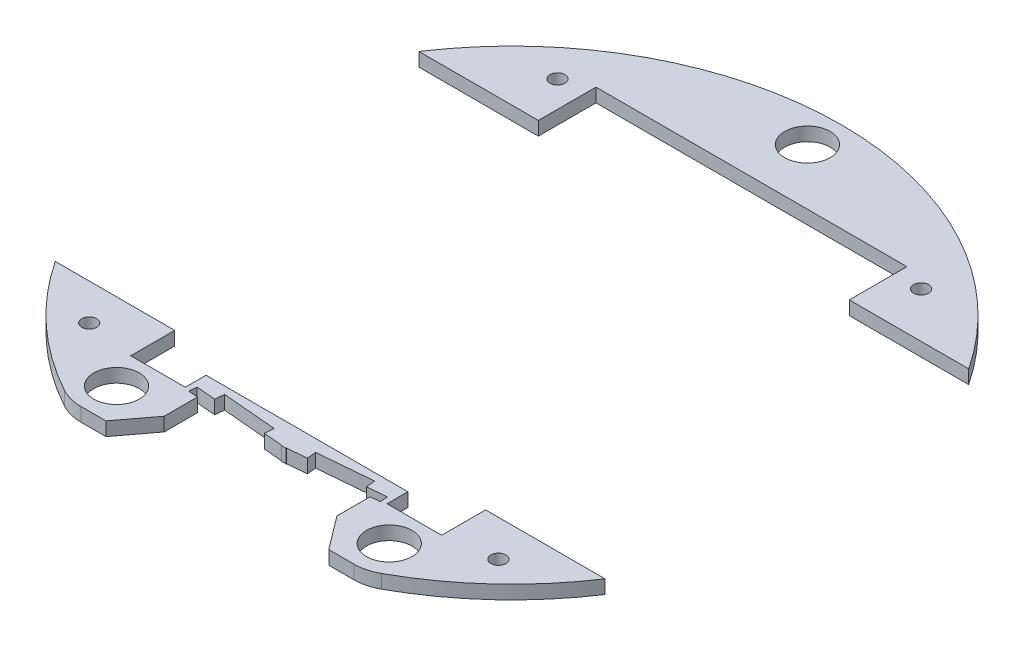
SolidWorks part; units mm, degrees
ref_plane "Front Plane" through (0, 0, 0) normal (0, 0, 1) x (1, 0, 0)
ref_plane "Top Plane" through (0, 0, 0) normal (0, 1, 0) x (1, 0, 0)
ref_plane "Right Plane" through (0, 0, 0) normal (1, 0, 0) x (0, 0, -1)
sketch "Sketch1" plane through (0, 0, 0) normal (0, 1, 0) x (1, 0, 0)
  line L0 (-30.03, -64.8129) -> (30.03, -64.8129)
  line L1 (0, -85) -> (0, 0) construction
  line L2 (0, -85) -> (32.4891, -64.8129) construction
  arc A0 (34.8348, -63.5829) -> (-34.8348, -63.5829) centre (0, 0) ccw
  circle A1 centre (0, -85) radius 38.25 construction
  arc A2 (30.03, -64.8129) -> (34.8348, -63.5829) centre (30.03, -54.8129) ccw
  arc A3 (-30.03, -64.8129) -> (-34.8348, -63.5829) centre (-30.03, -54.8129) cw
  dimension "D1" = 145
  dimension "D2" = 76.5
  dimension "D4" = 10
  dimension "D3" = 85
extrude "Boss-Extrude1" add sketch "Sketch1" along normal blind 3
sketch "Sketch2" plane through (0, 3, 0) normal (0, 1, 0) x (1, 0, 0)
  line L5 (22.2, -49.6757) -> (22.2, -45.1)
  line L6 (22.2, -45.1) -> (-22.2, -45.1)
  line L7 (-22.2, -45.1) -> (-22.2, -49.6757)
  line L8 (22.2, 49.6757) -> (22.2, 45.5)
  line L9 (-34.2, -49.6757) -> (-22.2, -49.6757) construction
  line L10 (-34.2, -49.6757) -> (-34.2, 49.6757) construction
  line L11 (-34.2, 49.6757) -> (-22.2, 49.6757) construction
  line L19 (34.2, 49.6757) -> (22.2, 49.6757) construction
  line L20 (34.2, -49.6757) -> (34.2, 49.6757) construction
  line L21 (34.2, -49.6757) -> (22.2, -49.6757) construction
  line L22 (22.2, 45.5) -> (-22.2, 45.5)
  line L23 (-22.2, 45.5) -> (-22.2, 49.6757)
  line L35 (-34.2, -49.6757) -> (-22.2, -49.6757)
  line L36 (-34.2, -49.6757) -> (-34.2, 49.6757)
  line L37 (-34.2, 49.6757) -> (-22.2, 49.6757)
  line L55 (34.2, 49.6757) -> (22.2, 49.6757)
  line L56 (34.2, -49.6757) -> (34.2, 49.6757)
  line L57 (34.2, -49.6757) -> (22.2, -49.6757)
  dimension "D1" = 45.1
  dimension "D2" = 45.5
extrude "Cut-Extrude1" cut sketch "Sketch2" against normal through all contours L55 L37 L36 L35 L7 L6 L5 L57 L56 region at (0, 3, -0.1256)
sketch "Sketch3" plane through (0, 3, 0) normal (0, 1, 0) x (1, 0, 0)
  line L0 (-34.2, 40) -> (-34.2, -40)
  line L1 (-72.5, -40) -> (-34.2, -40)
  line L2 (-72.5, -40) -> (-72.5, 40)
  line L3 (-72.5, 40) -> (-34.2, 40)
  line L4 (72.5, -40) -> (72.5, 40)
  line L5 (-72.5, -40) -> (72.5, 40) construction
  line L6 (-72.5, 40) -> (72.5, -40) construction
  line L7 (-34.2, -49.6757) -> (-34.2, 49.6757) construction
  line L8 (34.2, 40) -> (34.2, -40)
  line L9 (34.2, -49.6757) -> (34.2, 49.6757) construction
  line L10 (34.2, 40) -> (72.5, 40)
  line L11 (34.2, -40) -> (72.5, -40)
  arc A0 (34.8348, -63.5829) -> (-34.8348, -63.5829) centre (0, 0) ccw construction
  point P0 (0, 0)
  dimension "D1" = 80
extrude "Cut-Extrude2" cut sketch "Sketch3" against normal through all
sketch "Sketch4" plane through (0, 3, 0) normal (0, 1, 0) x (1, 0, 0)
  line L0 (-21.0702, -50.0262) -> (-0.6482, -51.8129)
  line L1 (21.0702, -50.0262) -> (20.922, -48.3326)
  line L2 (0.6482, -51.8129) -> (0.5, -50.1193)
  line L3 (20.922, -48.3326) -> (0.5, -50.1193)
  line L4 (0, 0) -> (0, -64.8129) construction
  line L5 (-30.03, -64.8129) -> (30.03, -64.8129) construction
  line L6 (-20.922, -48.3326) -> (-0.5, -50.1193)
  line L7 (-0.6482, -51.8129) -> (-0.5, -50.1193)
  line L8 (-21.0702, -50.0262) -> (-20.922, -48.3326)
  line L14 (21.0702, -50.0262) -> (0.6482, -51.8129)
  dimension "D1" = 1.7
  dimension "D2" = 20.5
  dimension "D3" = 5
  dimension "D4" = 13
  dimension "D5" = 0.5
extrude "Cut-Extrude3" cut sketch "Sketch4" against normal through all
sketch "Sketch5" plane through (0, 3, 0) normal (0, 1, 0) x (1, 0, 0)
  line L0 (-19, -64.8129) -> (-19, -50.2073)
  line L4 (0.6482, -51.8129) -> (21.0702, -50.0262) construction
  line L5 (16.6882, -48.7031) -> (4.7338, -49.7489)
  line L6 (16.6882, -48.7031) -> (16.5139, -46.7107)
  line L7 (4.7338, -49.7489) -> (4.5595, -47.7565)
  line L8 (16.5139, -46.7107) -> (4.5595, -47.7565)
  line L9 (20.922, -48.3326) -> (0.5, -50.1193) construction
  line L10 (0, 0) -> (0, -50.2073) construction
  line L11 (19, -64.8129) -> (19, -50.2073)
  line L13 (-16.5139, -46.7107) -> (-4.5595, -47.7565)
  line L14 (-4.7338, -49.7489) -> (-4.5595, -47.7565)
  line L15 (-16.6882, -48.7031) -> (-16.5139, -46.7107)
  line L16 (-16.6882, -48.7031) -> (-4.7338, -49.7489)
  line L22 (-30.03, -64.8129) -> (30.03, -64.8129) construction
  line L23 (19, -50.2073) -> (-19, -50.2073)
  line L25 (-19, -64.8129) -> (19, -64.8129)
  point P14 (10.711, -49.226)
  point P15 (10.711, -49.226)
  dimension "D1" = 12
  dimension "D2" = 38
  dimension "D4" = 2
extrude "Cut-Extrude4" cut sketch "Sketch5" against normal through all
sketch "Sketch6" plane through (0, 3, 0) normal (0, 1, 0) x (1, 0, 0)
  line L1 (34.2, 49.6757) -> (-34.2, 49.6757)
  line L2 (34.2, 49.6757) -> (34.2, 52.6757)
  line L3 (34.2, 52.6757) -> (-34.2, 52.6757)
  line L4 (-34.2, 49.6757) -> (-34.2, 52.6757)
  point P4 (-34.2, 49.6757)
  dimension "D1" = 3
extrude "Cut-Extrude5" cut sketch "Sketch6" against normal through all body kept at (60.4669, 0, -40)
sketch "Sketch7" plane through (0, 3, 0) normal (0, 1, 0) x (1, 0, 0)
  line L0 (0, 0) -> (0, -31.2827) construction
  circle A0 centre (-30, -57) radius 5
  circle A4 centre (30, -57) radius 5
  dimension "D1" = 10
  dimension "D2" = 30
  dimension "D3" = 57
extrude "Cut-Extrude6" cut sketch "Sketch7" against normal through all
sketch "Sketch11" plane through (0, 3, 0) normal (0, 1, 0) x (1, 0, 0)
  line L0 (0, 0) -> (0, 65) construction
  circle A0 centre (0, 65) radius 5
  dimension "D2" = 10
  dimension "D1" = 65
extrude "Cut-Extrude10" cut sketch "Sketch11" against normal through all
sketch "Sketch13" plane through (0, 3, 0) normal (0, 1, 0) x (1, 0, 0)
  line L0 (19, -57.5101) -> (24.515, -64.8129)
  line L1 (19, -64.8129) -> (19, -50.2073) construction
  line L2 (19, -64.8129) -> (30.03, -64.8129) construction
  line L3 (24.515, -64.8129) -> (19, -64.8129)
  line L4 (19, -64.8129) -> (19, -57.5101)
  line L5 (0, 0) -> (0, -25.0729) construction
  line L6 (-19, -64.8129) -> (-19, -57.5101)
  line L7 (-24.515, -64.8129) -> (-19, -64.8129)
  line L8 (-19, -57.5101) -> (-24.515, -64.8129)
extrude "Cut-Extrude11" cut sketch "Sketch13" against normal through all
sketch "Sketch14" plane through (0, 3, 0) normal (0, 1, 0) x (1, 0, 0)
  line L1 (0, 0) -> (0, -20.685) construction
  circle A0 centre (45, -48) radius 1.65
  circle A1 centre (-45, -48) radius 1.65
  circle A2 centre (40, 50) radius 1.65
  circle A3 centre (-40, 50) radius 1.65
  dimension "D3" = 3.3
  dimension "D1" = 45
  dimension "D2" = 48
  dimension "D4" = 40
  dimension "D5" = 50
extrude "Cut-Extrude12" cut sketch "Sketch14" against normal through all
equation "\"smallPulleyTeeth\"= 30"
equation "\"largePulleyTeeth\"= 30"
equation "\"eighthThick\"= 3.0mm"
equation "\"sixteenthThick\" = 1.7mm"
equation "\"quarterThick\"=6.0mm"
equation "\"OD\" = 145mm"
equation "\"puckAngle\" = 60.5deg"
equation "\"puckDiam\" = 76.5mm"
equation "\"axlePress\" = 5.9mm"
equation "\"press\" = 0.2mm"
equation "\"wheelClear\" = 0.3mm"
equation "\"10-32clear\" = 4.8mm"
equation "\"6-32clear\" = 3.3mm"
equation "\"8-32clear\" = 4.0mm"
equation "\"4-40clear\" = 3.0mm"
equation "\"wheelHeight\" = 22mm"
equation "\"wheelWell\" = 65mm"
equation "\"D1@Sketch1\"=\"OD\""
equation "\"D1@Boss-Extrude1\"=\"eighthThick\""
equation "\"D2@Sketch1\"=\"puckDiam\""
equation "\"puckDist\" = 85mm"
equation "\"scoopFillet\" = 5mm"
equation "\"10-32tap\" = 4.45mm"
equation "\"ledSmall\" = 3.1mm"
equation "\"ledLarge\" = 4.2mm"
equation "\"ledLength\" = 4.2mm"
equation "\"D3@Sketch1\"=\"puckDist\""
equation "\"D1@Sketch6\"=\"eighthThick\""
